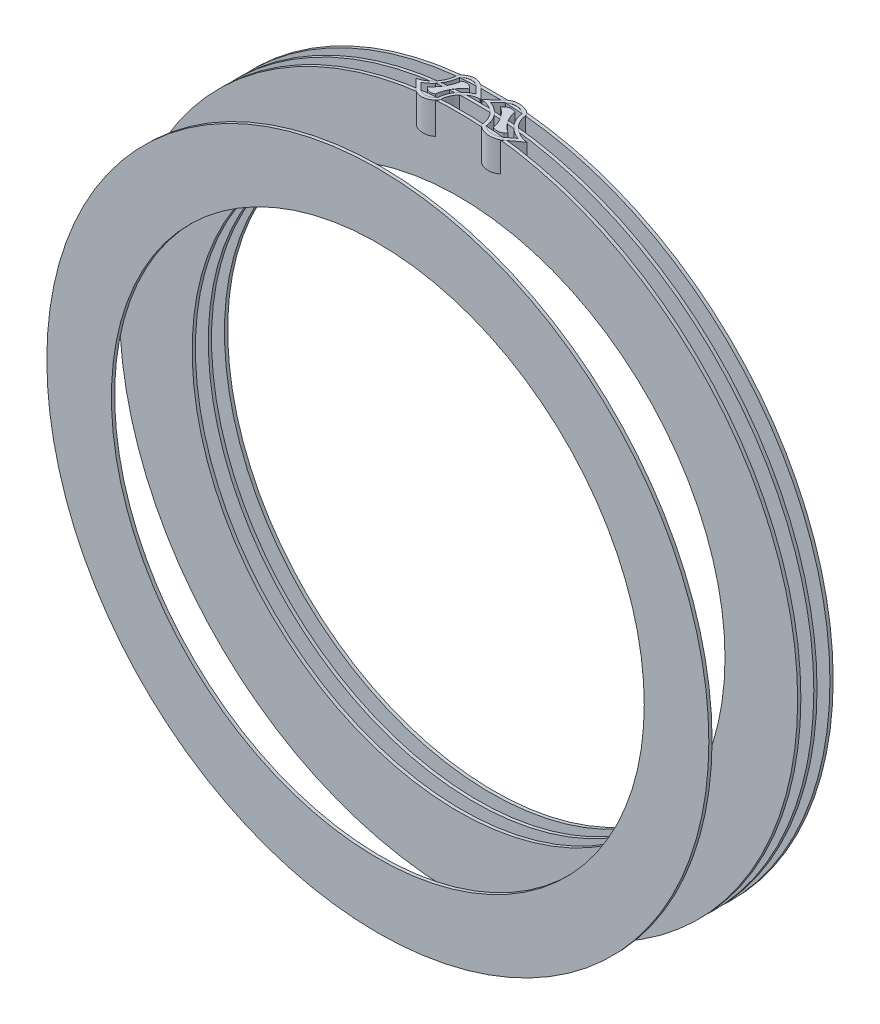
SolidWorks part; units mm, degrees
ref_plane "Front Plane" through (0, 0, 0) normal (0, 0, 1) x (1, 0, 0)
ref_plane "Top Plane" through (0, 0, 0) normal (0, 1, 0) x (1, 0, 0)
ref_plane "Right Plane" through (0, 0, 0) normal (1, 0, 0) x (0, 0, -1)
sketch "Sketch1" plane through (0, 0, 0) normal (0, 0, 1) x (1, 0, 0)
  circle A3 centre (0, 0) radius 10.4775
  circle A4 centre (0, 0) radius 13.6525
  circle A5 centre (0, 0) radius 13.0175
  circle A6 centre (0, 0) radius 12.3825
  dimension "D1" = 27.305
  dimension "D3" = 20.955
  dimension "D5" = 0.635
  dimension "D2" = 2.54
  dimension "D4" = 1.905
extrude "Boss-Extrude1" add sketch "Sketch1" along normal mid plane 0.127 contours A5 A6 | A6 A3
ref_plane "Plane1" through (0, 12.065, 0) normal (0, 1, 0) x (1, 0, 0)
sketch "Sketch3" plane through (0, 12.065, 0) normal (0, 1, 0) x (1, 0, 0)
  line L0 (0, 4.445) -> (0, 0)
  line L2 (1.5055, 3.3995) -> (1.5818, 3.4758)
  line L3 (1.3466, 4.445) -> (2.1791, 4.445)
  line L4 (0.46, 4.445) -> (0.0322, 4.0171)
  line L5 (1.73, 3.175) -> (2.1788, 3.6237)
  line L6 (1.3677, 4.318) -> (2.1791, 4.318)
  line L7 (1.857, 3.302) -> (2.179, 3.302)
  line L8 (2.179, 3.302) -> (2.179, 3.175)
  line L9 (2.179, 3.175) -> (1.73, 3.175)
  line L10 (2.1791, 4.445) -> (2.1791, 4.318)
  line L11 (1.6402, 3.2648) -> (1.9111, 3.5357)
  line L12 (0.5498, 4.3552) -> (0.279, 4.0843)
  line L13 (0.6845, 4.2205) -> (0.6083, 4.1442)
  line L14 (-0.6845, 4.2205) -> (-0.6083, 4.1442)
  line L15 (-0.5498, 4.3552) -> (-0.279, 4.0843)
  line L16 (-1.6402, 3.2648) -> (-1.9111, 3.5357)
  line L17 (-2.1791, 4.445) -> (-2.1791, 4.318)
  line L18 (-2.179, 3.175) -> (-1.73, 3.175)
  line L19 (-2.179, 3.302) -> (-2.179, 3.175)
  line L20 (-1.857, 3.302) -> (-2.179, 3.302)
  line L21 (-1.3677, 4.318) -> (-2.1791, 4.318)
  line L22 (-1.73, 3.175) -> (-2.1788, 3.6237)
  line L23 (-0.46, 4.445) -> (-0.0322, 4.0171)
  line L24 (-1.3466, 4.445) -> (-2.1791, 4.445)
  line L25 (-1.5055, 3.3995) -> (-1.5818, 3.4758)
  arc A0 (1.73, 3.175) -> (0.8763, 3.1347) centre (1.281, 3.624) cw
  arc A1 (1.3042, 4.493) -> (0.46, 4.445) centre (0.9091, 3.996) ccw
  arc A2 (0.0407, 3.9955) -> (0.8305, 3.2248) centre (0.011, 3.175) cw
  arc A3 (1.3602, 4.3824) -> (2.1788, 3.6237) centre (2.1791, 4.445) ccw
  arc A4 (0.8305, 3.2248) -> (0.8763, 3.1347) centre (0.9573, 3.2326) ccw
  arc A5 (1.3602, 4.3824) -> (1.3042, 4.493) centre (1.2328, 4.3875) ccw
  arc A6 (1.2328, 4.3875) -> (0.5498, 4.3552) centre (0.9091, 3.996) ccw
  arc A7 (-0.0322, 4.0171) -> (-0.0407, 3.9955) centre (-0.0411, 4.0081) cw
  arc A8 (1.2328, 4.3875) -> (1.9111, 3.5357) centre (2.1791, 4.445) ccw
  arc A9 (0.279, 4.0843) -> (0.9573, 3.2326) centre (0.011, 3.175) cw
  arc A10 (1.6402, 3.2648) -> (0.9573, 3.2326) centre (1.281, 3.624) cw
  arc A11 (1.0527, 4.2791) -> (0.6845, 4.2205) centre (0.9091, 3.996) ccw
  arc A12 (1.0527, 4.2791) -> (1.5818, 3.4758) centre (2.1791, 4.445) ccw
  arc A13 (0.6083, 4.1442) -> (1.1374, 3.3409) centre (0.011, 3.175) cw
  arc A14 (1.5055, 3.3995) -> (1.1374, 3.3409) centre (1.281, 3.624) cw
  arc A15 (0.0322, 4.0171) -> (0.0407, 3.9955) centre (0.0411, 4.0081) ccw
  arc A16 (-1.5055, 3.3995) -> (-1.1374, 3.3409) centre (-1.281, 3.624) ccw
  arc A17 (-0.6083, 4.1442) -> (-1.1374, 3.3409) centre (-0.011, 3.175) ccw
  arc A18 (-1.0527, 4.2791) -> (-1.5818, 3.4758) centre (-2.1791, 4.445) cw
  arc A19 (-1.0527, 4.2791) -> (-0.6845, 4.2205) centre (-0.9091, 3.996) cw
  arc A20 (-1.6402, 3.2648) -> (-0.9573, 3.2326) centre (-1.281, 3.624) ccw
  arc A21 (-0.279, 4.0843) -> (-0.9573, 3.2326) centre (-0.011, 3.175) ccw
  arc A22 (-1.2328, 4.3875) -> (-1.9111, 3.5357) centre (-2.1791, 4.445) cw
  arc A23 (-1.2328, 4.3875) -> (-0.5498, 4.3552) centre (-0.9091, 3.996) cw
  arc A24 (-1.3602, 4.3824) -> (-1.3042, 4.493) centre (-1.2328, 4.3875) cw
  arc A25 (-0.8305, 3.2248) -> (-0.8763, 3.1347) centre (-0.9573, 3.2326) cw
  arc A26 (-1.3602, 4.3824) -> (-2.1788, 3.6237) centre (-2.1791, 4.445) cw
  arc A27 (-0.0407, 3.9955) -> (-0.8305, 3.2248) centre (-0.011, 3.175) ccw
  arc A28 (-1.3042, 4.493) -> (-0.46, 4.445) centre (-0.9091, 3.996) cw
  arc A29 (-1.73, 3.175) -> (-0.8763, 3.1347) centre (-1.281, 3.624) ccw
  dimension "D1" = 0.635
extrude "Boss-Extrude3" add sketch "Sketch3" along normal offset from surface (1.2061 mm away) 0.3175 contours L4 A15 A2 A4 A0 L5 A3 A5 A1 L11 A10 A9 L12 A6 A8 | A19 A18 L25 A16 A17 L14 | L22 A29 A25 A27 A7 L23 A28 A24 A26 A22 A23 L15 A21 A20 L16 | A11 L13 A13 A14 L2 A12
ref_plane "Plane2" through (0, 0, -3.175) normal (0, 0, 1) x (1, 0, 0)
ref_plane "Plane3" through (0, 0, -3.81) normal (0, 0, 1) x (1, 0, 0)
ref_plane "Plane4" through (0, 0, -4.445) normal (0, 0, 1) x (1, 0, 0)
sketch "Sketch4" plane through (0, 0, -3.175) normal (0, 0, 1) x (1, 0, 0)
  circle A0 centre (0, 0) radius 10.4775
  circle A1 centre (0, 0) radius 13.335
extrude "Boss-Extrude4" add sketch "Sketch4" along normal mid plane 0.127
sketch "Sketch9" plane through (0, 0, -3.81) normal (0, 0, 1) x (1, 0, 0)
  circle A0 centre (0, 0) radius 10.4775
  circle A1 centre (0, 0) radius 13.335
extrude "Boss-Extrude5" add sketch "Sketch9" along normal mid plane 0.127
sketch "Sketch10" plane through (0, 0, -4.445) normal (0, 0, 1) x (1, 0, 0)
  circle A0 centre (0, 0) radius 10.4775
  circle A1 centre (0, 0) radius 13.335
extrude "Boss-Extrude6" add sketch "Sketch10" along normal mid plane 0.127
ref_plane "Plane7" through (1.905, 0, 0) normal (1, 0, 0) x (0, 0, -1)
sketch "Sketch11" plane through (1.905, 0, 0) normal (1, 0, 0) x (0, 0, -1)
  line L0 (0.0635, 12.065) -> (2.9794, 12.065) construction
  line L3 (2.582, 12.065) -> (-2.582, 12.065) construction
  line L4 (0.0635, -13.0175) -> (0.0635, 13.0175) construction
  line L5 (1.5214, 12.065) -> (1.5214, 12.077) construction
  circle A2 centre (1.5214, 12.077) radius 0.381
ref_plane "Plane8" through (0, 0, -1.651) normal (0, 0, 1) x (1, 0, 0)
ref_plane "Plane9" through (0, 11.557, 0) normal (0, 1, 0) x (1, 0, 0)
ref_plane "Plane10" through (0, 0, 0) normal (1, 0, 0) x (0, 0, -1)
